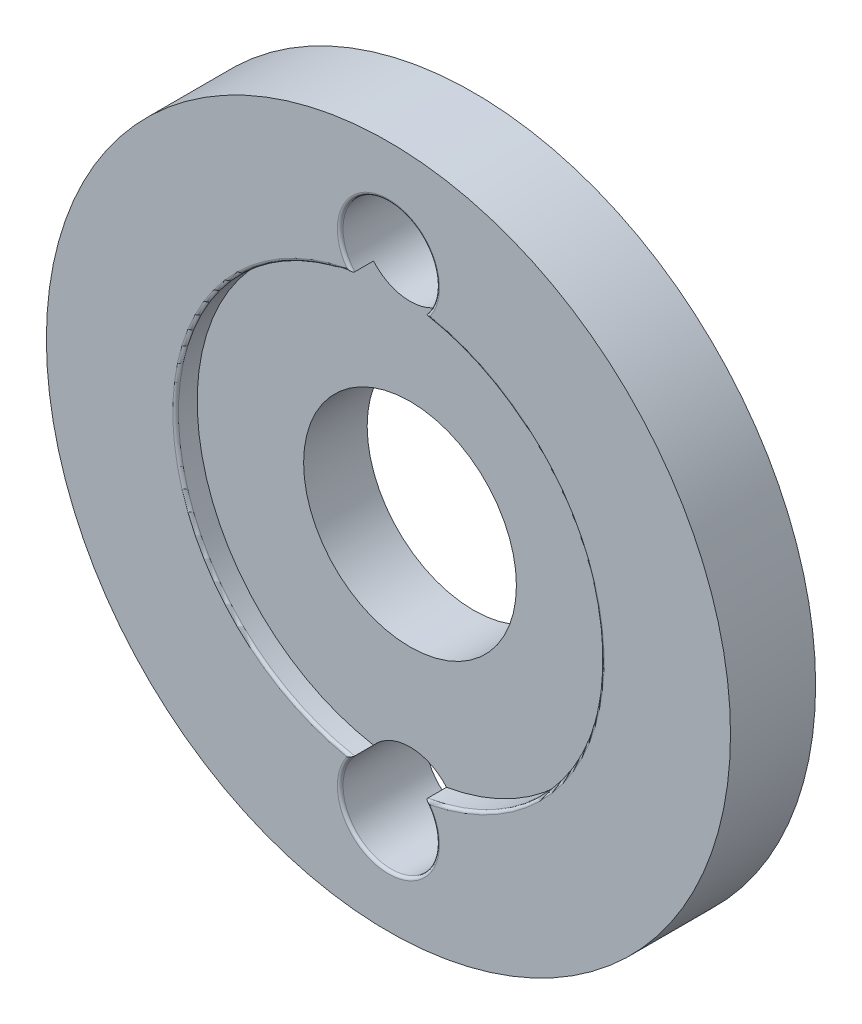
SolidWorks part; units mm, degrees
ref_plane "Plano frontal" through (0, 0, 0) normal (0, 0, 1) x (1, 0, 0)
ref_plane "Plano superior" through (0, 0, 0) normal (0, 1, 0) x (1, 0, 0)
ref_plane "Plano direito" through (0, 0, 0) normal (1, 0, 0) x (0, 0, -1)
sketch "Esboço2" plane through (0, 0, 0) normal (0, 0, 1) x (1, 0, 0)
  circle A0 centre (0, 0) radius 12.0556
  circle A5 centre (0, 0) radius 3.75
  arc A8 (-7.3827, -1.3213) -> (7.3827, 1.3213) centre (0, 0) ccw
  arc A9 (-7.3827, -1.3213) -> (-1.2866, -7.3888) centre (0, 0) ccw
  arc A10 (7.3827, 1.3213) -> (-7.3827, -1.3213) centre (0, 0) ccw
  arc A11 (7.3827, 1.3213) -> (1.2866, 7.3888) centre (0, 0) ccw
  arc A16 (1.2866, -7.3888) -> (7.3827, 1.3213) centre (0, 0) ccw
  arc A17 (-1.2866, 7.3888) -> (-7.3827, -1.3213) centre (0, 0) ccw
  circle A18 centre (0, -8.5) radius 1.7
  circle A19 centre (0, 8.5) radius 1.7
  circle A20 centre (0, -8.5) radius 1.25
  circle A21 centre (0, 8.5) radius 1.25
  dimension "D1" = 7.5
  dimension "D2" = 3.4
  dimension "D3" = 3.4
extrude "Ressalto-extrusão6" add sketch "Esboço2" along normal blind 2.24 contours A19 A17 A9 A18 A16 A11 A5 region at (-5.9721, 4.1798, 0)
extrude "Ressalto-extrusão7" add sketch "Esboço2<6>" along normal blind 3 contours A0 A19 A11 A16 A18 A9 A17 region at (-11.7146, 0, 0)
sketch "Esboço2<6>" plane through (0, 0, 0) normal (0, 0, 1) x (1, 0, 0) same geometry as "Esboço2"
fillet "Filete3" radius 0.1 4 edges at (0, -10.2, 3) (7.5, 0, 3) (-7.5, 0, 3) (0, 10.2, 3)
